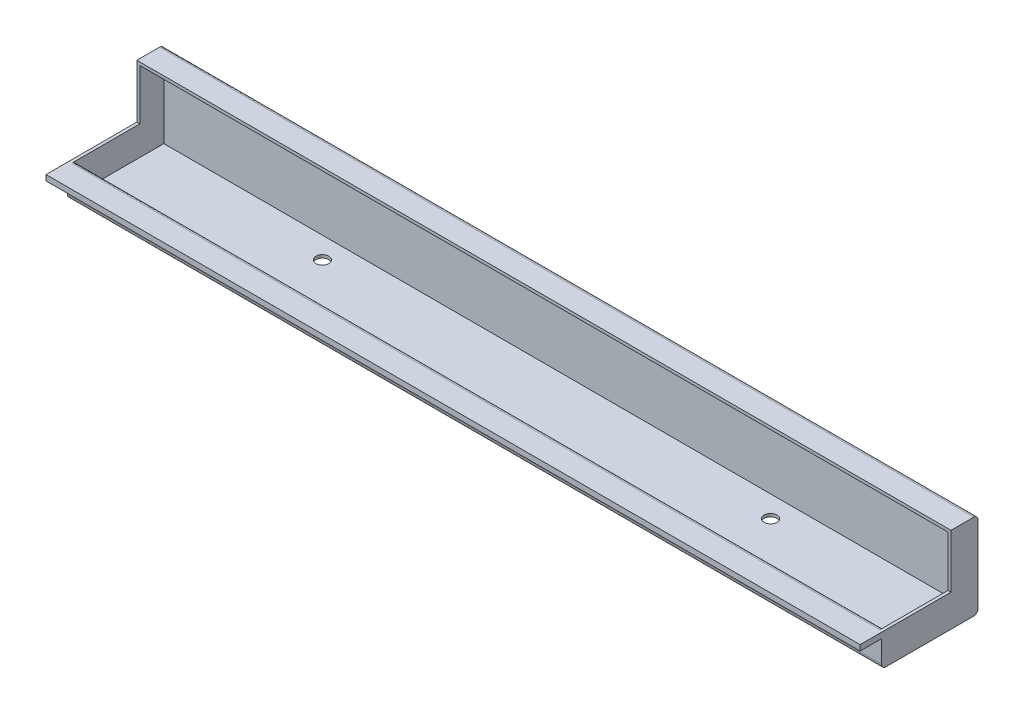
SolidWorks part; units mm, degrees
ref_plane "Front Plane" through (0, 0, 0) normal (0, 0, 1) x (1, 0, 0)
ref_plane "Top Plane" through (0, 0, 0) normal (0, 1, 0) x (1, 0, 0)
ref_plane "Right Plane" through (0, 0, 0) normal (1, 0, 0) x (0, 0, -1)
sketch "Sketch1" plane through (0, 0, 0) normal (0, 0, 1) x (1, 0, 0)
  line L1 (-241.3, -25.4) -> (241.3, -25.4)
  line L2 (-241.3, -25.4) -> (-241.3, 25.4)
  line L3 (-241.3, 25.4) -> (241.3, 25.4)
  line L4 (241.3, -25.4) -> (241.3, 25.4)
  line L5 (-241.3, -25.4) -> (241.3, 25.4) construction
  line L6 (-241.3, 25.4) -> (241.3, -25.4) construction
  point P0 (0, 0)
  dimension "D1" = 482.6
  dimension "D2" = 50.8
extrude "Boss-Extrude1" add sketch "Sketch1" along normal blind 69.85
sketch "Sketch2" plane through (0, 25.4, 0) normal (0, 1, 0) x (1, 0, 0)
  line L0 (241.3, -69.85) -> (241.3, 0) construction
  line L1 (-241.3, 0) -> (241.3, 0)
  line L2 (-241.3, 0) -> (-241.3, -16.002)
  line L3 (-241.3, -16.002) -> (241.3, -16.002)
  line L4 (241.3, 0) -> (241.3, -16.002)
  line L5 (-241.3, -34.925) -> (-219.8341, -34.925)
  line L6 (-241.3, -69.85) -> (-241.3, 0) construction
  line L7 (241.3, -69.85) -> (241.3, -53.848)
  line L8 (-241.3, -69.85) -> (-241.3, -53.848)
  line L9 (-241.3, -69.85) -> (241.3, -69.85)
  line L10 (-241.3, -53.848) -> (241.3, -53.848)
  line M6 (-241.3, 0) -> (-241.3, -69.85)
  line M8 (241.3, -69.85) -> (241.3, 0)
  dimension "D1" = 16.002
extrude "Cut-Extrude2" cut sketch "Sketch2" against normal blind 49.022 contours L10 L3 M6 M8 region at (0, 25.4, 34.925)
sketch "Sketch3" plane through (0, 25.4, 0) normal (0, 1, 0) x (1, 0, 0)
  line L1 (-241.3, -53.848) -> (241.3, -53.848)
  line L2 (-241.3, -53.848) -> (-241.3, -69.85)
  line L3 (-241.3, -69.85) -> (241.3, -69.85)
  line L4 (241.3, -53.848) -> (241.3, -69.85)
extrude "Cut-Extrude3" cut sketch "Sketch3" against normal blind 31.75
sketch "Sketch4" plane through (0, 0, 69.85) normal (0, 0, 1) x (1, 0, 0)
  line L0 (241.3, -25.4) -> (241.3, -6.35) construction
  line L1 (-241.3, -25.4) -> (241.3, -25.4)
  line L2 (-241.3, -25.4) -> (-241.3, -9.652)
  line L3 (-241.3, -9.652) -> (241.3, -9.652)
  line L4 (241.3, -25.4) -> (241.3, -9.652)
  line L5 (-241.3, -6.35) -> (241.3, -6.35) construction
  dimension "D1" = 3.302
extrude "Cut-Extrude4" cut sketch "Sketch4" against normal blind 12.7
shell "Shell2" thickness 1.778 removed face at (0, 0.889, 16.002)
sketch "Sketch5" plane through (0, 0, 53.848) normal (0, 0, -1) x (-1, 0, 0)
  line L0 (-241.3, -6.35) -> (241.3, -6.35) construction
  line L1 (241.3, -23.622) -> (239.522, -23.622)
  line L2 (241.3, -23.622) -> (241.3, -6.35)
  line L3 (241.3, -6.35) -> (239.522, -6.35)
  line L4 (239.522, -23.622) -> (239.522, -6.35)
  line L5 (0, -23.622) -> (0, -9.0933)
  line L6 (241.3, -23.622) -> (-241.3, -23.622) construction
  line L7 (-239.522, -23.622) -> (-239.522, -6.35)
  line L8 (-241.3, -6.35) -> (-239.522, -6.35)
  line L9 (-241.3, -23.622) -> (-241.3, -6.35)
  line L10 (-241.3, -23.622) -> (-239.522, -23.622)
  line M2 (241.3, -6.35) -> (-241.3, -6.35)
  line M4 (-241.3, -23.622) -> (241.3, -23.622)
  line M5 (241.3, -23.622) -> (241.3, -6.35)
  dimension "D1" = 1.778
extrude "Boss-Extrude2" add sketch "Sketch5" along normal blind 44.45 contours L4 M4 M5 M2 | L7 L8 L9 L10 region at (-240.411, -14.986, 53.848)
fillet "Fillet1" radius 2.54 4 edges at (0, -6.35, 53.848) (0, -25.4, 57.15) (0, -25.4, 0) (0, 25.4, 0)
sketch "Sketch6" plane through (0, -23.622, 0) normal (0, 1, 0) x (1, 0, 0)
  line L0 (-239.522, -1.778) -> (-239.522, -14.478)
  line L1 (-239.522, -53.848) -> (-239.522, -1.778) construction
  line L2 (-239.522, -14.478) -> (-132.842, -14.478)
  line L3 (0, -1.778) -> (0, -14.478)
  line L4 (-239.522, -1.778) -> (239.522, -1.778) construction
  circle A0 centre (-132.842, -14.478) radius 3.81
  circle A1 centre (132.842, -14.478) radius 3.81
  dimension "D1" = 12.7
  dimension "D2" = 106.68
extrude "Cut-Extrude5" cut sketch "Sketch6" against normal blind 44.45 contours A0 | A1 region at (-132.842, -23.622, 18.1802)
